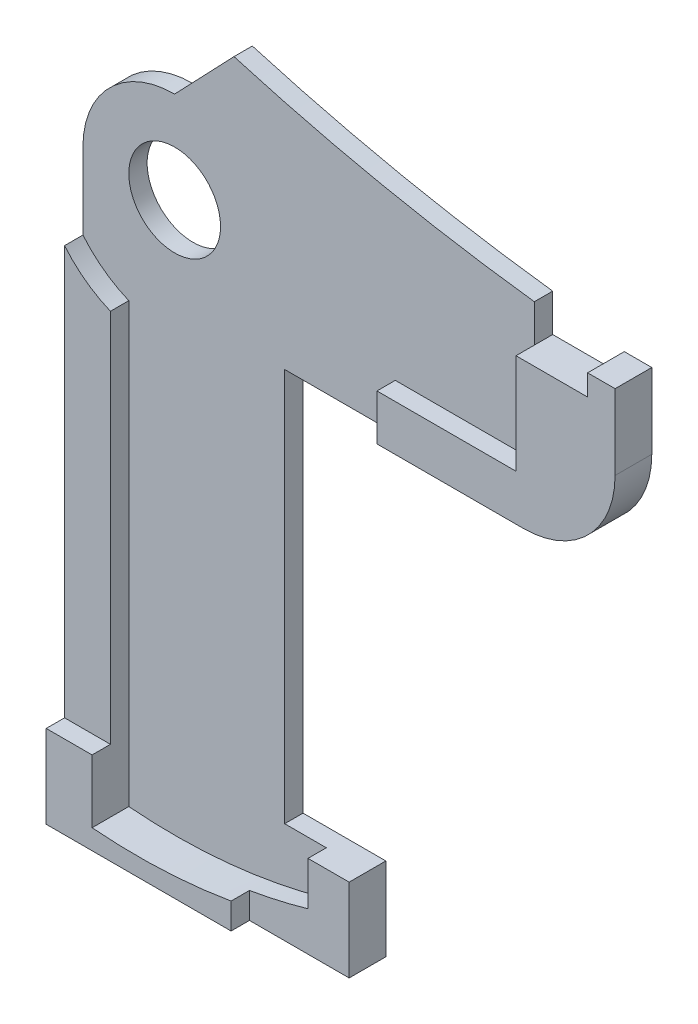
SolidWorks part; units mm, degrees
ref_plane "정면" through (0, 0, 0) normal (0, 0, 1) x (1, 0, 0)
ref_plane "윗면" through (0, 0, 0) normal (0, 1, 0) x (1, 0, 0)
ref_plane "우측면" through (0, 0, 0) normal (1, 0, 0) x (0, 0, -1)
sketch "스케치1" plane through (0, 0, 0) normal (0, 0, 1) x (1, 0, 0)
  line L0 (0, 5) -> (3.2319, 8.3833)
  line L1 (0, 5) -> (19.6, 5)
  line L2 (19.6, 5) -> (19.6, 2.9507)
  line L3 (19.6, 2.9507) -> (23.5025, 2.9507)
  line L4 (23.5025, 2.9507) -> (23.5025, 4.0959)
  line L5 (23.5025, 4.0959) -> (25, 4.0959)
  line L6 (25, 4.0959) -> (25, 0)
  line L7 (20, -5) -> (5.9949, -5)
  line L8 (5.9949, -5) -> (5.9949, -26.4377)
  line L9 (-5, -30.9618) -> (10.5083, -30.9618)
  line L10 (-5, -30.9618) -> (-5, 0)
  line L11 (10.5083, -30.9618) -> (10.5083, -26.4377)
  line L12 (10.5083, -26.4377) -> (5.9949, -26.4377)
  line L13 (5.9949, -26.4377) -> (8.2516, -26.4377)
  line L14 (19.6, 2.9507) -> (19.6, -2.5)
  line L15 (19.6, -2.5) -> (12.0232, -2.5)
  line L16 (-2.5, -4.3301) -> (-2.5, -26.4377)
  line L17 (-2.5, -29.8745) -> (-2.5, -26.4377)
  line L18 (-2.5, -26.4377) -> (-5, -26.4377)
  line L19 (5.0761, -29.546) -> (5.0761, -30.9618)
  line L21 (8.2649, -26.4377) -> (8.2649, -28.8171)
  line L22 (12.0232, -2.5) -> (12.0232, -5)
  circle A0 centre (0, 0) radius 2.5
  circle A1 centre (0, 0) radius 5
  arc A2 (-2.5, -29.8745) -> (8.2649, -28.8171) centre (0, 0) ccw
  arc A3 (-5, -4.1533) -> (-2.5, -6) centre (0, 0) ccw
  arc A4 (19.6, 5) -> (3.2319, 8.3833) centre (32.2465, 107.4683) cw
  arc A5 (25, 0) -> (20, -5) centre (20, 0) cw
  dimension "D1" = 5
  dimension "D2" = 19.6
  dimension "D3" = 5
  dimension "D4" = 30
  dimension "D5" = 1.4975
extrude "보스-돌출3" add sketch "스케치1" along normal blind 3 contours A2 L17 L18 L10 L9 L19 region at (-3.75, -26.5481, 0)
extrude "보스-돌출4" add sketch "스케치1<7>" along normal blind 2 contours A2 L19 L9 L11 | L15 L7 L6 L5 L4 L3 L14 | A1 L10 L18 L16 region at (20.1008, -1.5139, 0) region at (-3.7678, -15.8289, 0) region at (8.4624, -29.1873, 0)
sketch "스케치1<7>" plane through (0, 0, 0) normal (0, 0, 1) x (1, 0, 0) same geometry as "스케치1"
extrude "보스-돌출5" add sketch "스케치1<8>" along normal blind 1 contours L17 A2 L11 L12 L8 L15 L14 L2 L1 A1 L10 L18 | A1 A0 | L10 A3 L16 A1 | L1 A4 L0 region at (7.1251, 6.0723, 0) region at (5.4757, -10.6185, 0) region at (3.4355, 3.4355, 0) region at (-3.8947, -3.9886, 0)
sketch "스케치1<8>" plane through (0, 0, 0) normal (0, 0, 1) x (1, 0, 0) same geometry as "스케치1"
